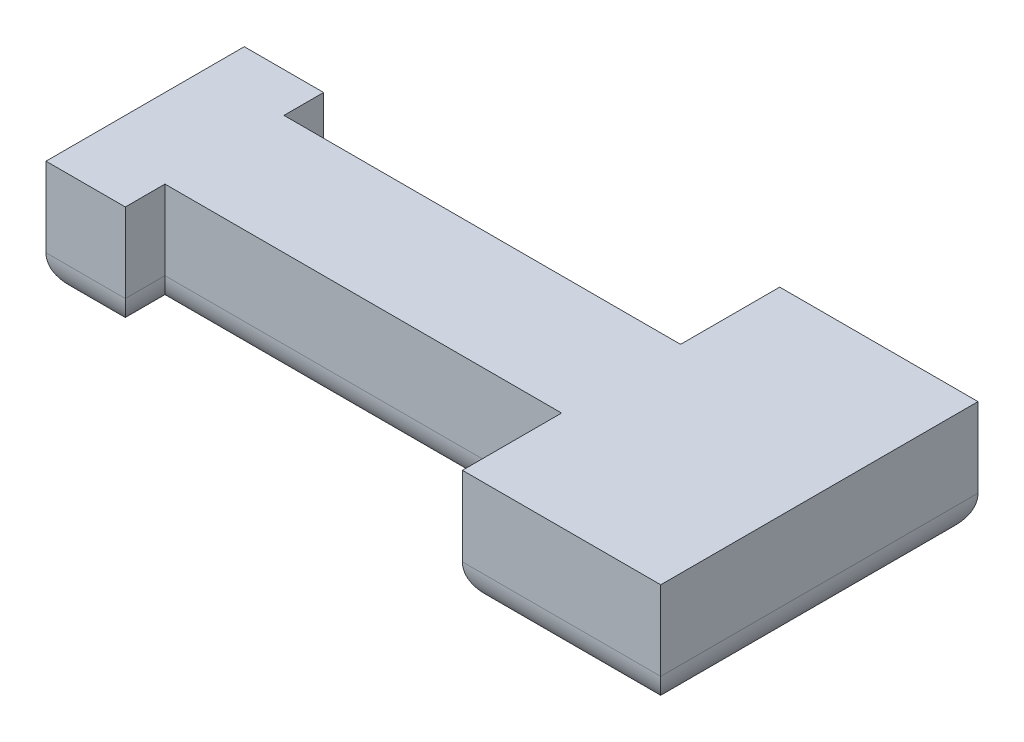
SolidWorks part; units mm, degrees
ref_plane "Front Plane" through (0, 0, 0) normal (0, 0, 1) x (1, 0, 0)
ref_plane "Top Plane" through (0, 0, 0) normal (0, 1, 0) x (1, 0, 0)
ref_plane "Right Plane" through (0, 0, 0) normal (1, 0, 0) x (0, 0, -1)
sketch "Sketch1" plane through (0, 0, 0) normal (0, 1, 0) x (1, 0, 0)
  line L0 (-12.5, -1.5) -> (-12.5, -2.5)
  line L1 (-2.5, 4) -> (2.5, 4)
  line L2 (-2.5, 4) -> (-2.5, 1.5)
  line L3 (-2.5, -4) -> (2.5, -4)
  line L4 (2.5, 4) -> (2.5, -4)
  line L5 (-2.5, 4) -> (2.5, -4) construction
  line L6 (-2.5, -4) -> (2.5, 4) construction
  line L7 (-2.5, 1.5) -> (-12.5, 1.5)
  line L9 (-2.5, -1.5) -> (-12.5, -1.5)
  line L11 (-14.5, 2.5) -> (-12.5, 2.5)
  line L12 (-14.5, 2.5) -> (-14.5, -2.5)
  line L13 (-14.5, -2.5) -> (-12.5, -2.5)
  line L14 (-12.5, 2.5) -> (-12.5, 1.5)
  line L15 (-2.5, -1.5) -> (-2.5, -4)
  point P0 (0, 0)
  dimension "D1" = 5
  dimension "D2" = 8
  dimension "D3" = 10
  dimension "D4" = 2
  dimension "D5" = 5
  dimension "D6" = 1
  dimension "D7" = 3
  dimension "D8" = 2.5
extrude "Boss-Extrude1" add sketch "Sketch1" along normal blind 3
sketch "Sketch2" plane through (0, 3, 0) normal (0, 1, 0) x (1, 0, 0)
  line L1 (-14.5, 2.5) -> (-12.5, 2.5)
  line L2 (-14.5, 2.5) -> (-14.5, -2.5)
  line L3 (-14.5, -2.5) -> (-12.5, -2.5)
  line L4 (-12.5, 2.5) -> (-12.5, -2.5)
fillet "Fillet2" radius 1 12 edges at (0, 0, -4) (-2.5, 0, -2.75) (-7.5, 0, -1.5) (-12.5, 0, -2) (-13.5, 0, -2.5) (-14.5, 0, 0) (-13.5, 0, 2.5) (-12.5, 0, 2) (-7.5, 0, 1.5) (-2.5, 0, 2.75) (0, 0, 4) (2.5, 0, 0)
